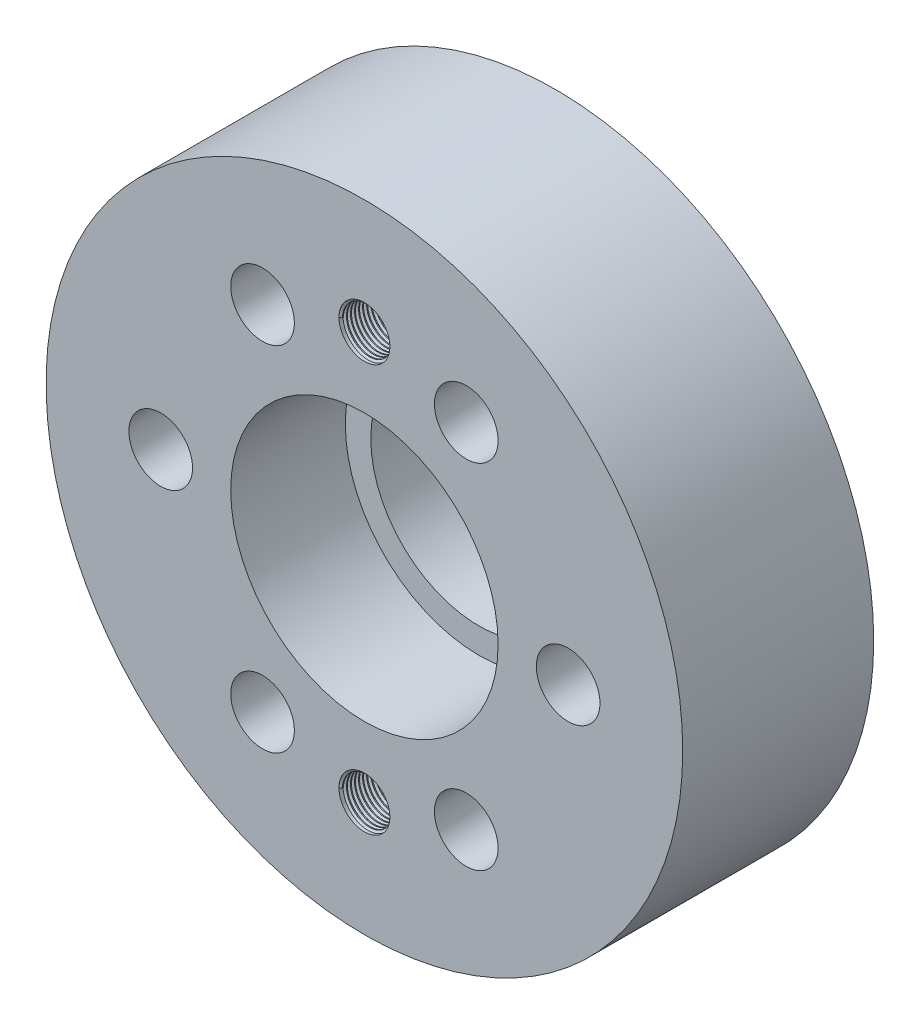
SolidWorks part; units mm, degrees
ref_plane "Plan de face" through (0, 0, 0) normal (0, 0, 1) x (1, 0, 0)
ref_plane "Plan de dessus" through (0, 0, 0) normal (0, 1, 0) x (1, 0, 0)
ref_plane "Plan de droite" through (0, 0, 0) normal (1, 0, 0) x (0, 0, -1)
sketch "Esquisse1" plane through (0, 0, 0) normal (0, 0, 1) x (1, 0, 0)
  circle A0 centre (0, 0) radius 8.5
  circle A1 centre (0, 0) radius 25
  dimension "D1" = 17
  dimension "D2" = 50
extrude "Boss.-Extru.1" add sketch "Esquisse1" along normal blind 15
sketch "Esquisse2" plane through (0, 0, 15) normal (0, 0, 1) x (1, 0, 0)
  circle A0 centre (0, 0) radius 10.5
  dimension "D1" = 21
extrude "Enlèv. mat.-Extru.1" cut sketch "Esquisse2" against normal blind 9
sketch "Esquisse3" plane through (0, 0, 15) normal (0, 0, 1) x (1, 0, 0)
  line L0 (0, 25) -> (0, -25) construction
  line L1 (-21.6506, 12.5) -> (21.6506, -12.5) construction
  line L2 (21.6506, 12.5) -> (-21.6506, -12.5) construction
  line L3 (0, 0) -> (25, 0) construction
  circle A0 centre (0, 0) radius 25 construction
  arc A1 (0, 25) -> (-21.6506, 12.5) centre (0, 0) ccw
  arc A2 (0, 25) -> (21.6506, 12.5) centre (0, 0) ccw
  circle A3 centre (0, 16) radius 2
  circle A4 centre (0, -16) radius 2
  circle A5 centre (16, 0) radius 2.5
  circle A6 centre (8, 13.8564) radius 2.5
  circle A7 centre (-8, 13.8564) radius 2.5
  circle A8 centre (-16, 0) radius 2.5
  circle A9 centre (-8, -13.8564) radius 2.5
  circle A10 centre (8, -13.8564) radius 2.5
  dimension "D1" = 4
  dimension "D3" = 4
  dimension "D5" = 5
  dimension "D2" = 16
  dimension "D4" = 16
  dimension "D6" = 16
  dimension "D7" = 16
extrude "Enlèv. mat.-Extru.2" cut sketch "Esquisse3" against normal blind 5.2 contours A7 | A8 | A9 | A6 | A10 | A5 region at (-8, 13.8564, 15) region at (-16, 0, 15) region at (-8, -13.8564, 15)
sketch "Esquisse4" plane through (0, 0, 15) normal (0, 0, 1) x (1, 0, 0)
  line L0 (0, 25) -> (0, -25) construction
  circle A0 centre (0, 0) radius 25 construction
  circle A1 centre (0, -16) radius 2
  circle A2 centre (0, 16) radius 2
  dimension "D1" = 4
  dimension "D2" = 4
  dimension "D3" = 16
  dimension "D4" = 16
extrude "Enlèv. mat.-Extru.3" cut sketch "Esquisse4" against normal blind 38.2
sketch "Esquisse5" plane through (0, 0, 0) normal (0, 0, -1) x (-1, 0, 0)
  circle A0 centre (0, 16) radius 3
  circle A1 centre (0, -16) radius 3
  dimension "D1" = 6
  dimension "D2" = 6
extrude "Enlèv. mat.-Extru.4" cut sketch "Esquisse5" against normal blind 11.2
thread "Filetage1" pitch 0.3175 method extrude profile "Profil de filetage1" start angle 0, offset 0, length 3, pitch 0.3175, diameter 4
ref_plane "Plan1" through (-2, 16, 15) normal (0, -1, 0) x (-1, 0, 0)
sketch "Profil de filetage1" plane through (-2, 16, 15) normal (0, -1, 0) x (-1, 0, 0)
  line L0 (0, 0) -> (0, 0.3175) construction
  line L11 (0, 0) -> (0, 0.2778)
  line L12 (0, 0.2778) -> (-0.1719, 0.1786)
  line L13 (-0.1719, 0.1786) -> (-0.1719, 0.0992)
  line L15 (-0.1719, 0.0992) -> (0, 0)
  line L17 (-0.1719, 0.1389) -> (0, 0.1389) construction
  point P2 (0, 0)
  dimension "Pitch" = 0.3175
  dimension "Profile_Angle" = 60
  dimension "Profile_Land" = 0.0794
  dimension "Profile_Height" = 0.1719
thread "Filetage2" pitch 0.3175 method extrude profile "Profil de filetage2" start angle 0, offset 0, length 3, pitch 0.3175, diameter 4
ref_plane "Plan2" through (-2, -16, 15) normal (0, -1, 0) x (-1, 0, 0)
sketch "Profil de filetage2" plane through (-2, -16, 15) normal (0, -1, 0) x (-1, 0, 0)
  line L0 (0, 0) -> (0, 0.3175) construction
  line L11 (0, 0) -> (0, 0.2778)
  line L12 (0, 0.2778) -> (-0.1719, 0.1786)
  line L13 (-0.1719, 0.1786) -> (-0.1719, 0.0992)
  line L15 (-0.1719, 0.0992) -> (0, 0)
  line L17 (-0.1719, 0.1389) -> (0, 0.1389) construction
  point P2 (0, 0)
  dimension "Pitch" = 0.3175
  dimension "Profile_Angle" = 60
  dimension "Profile_Land" = 0.0794
  dimension "Profile_Height" = 0.1719
